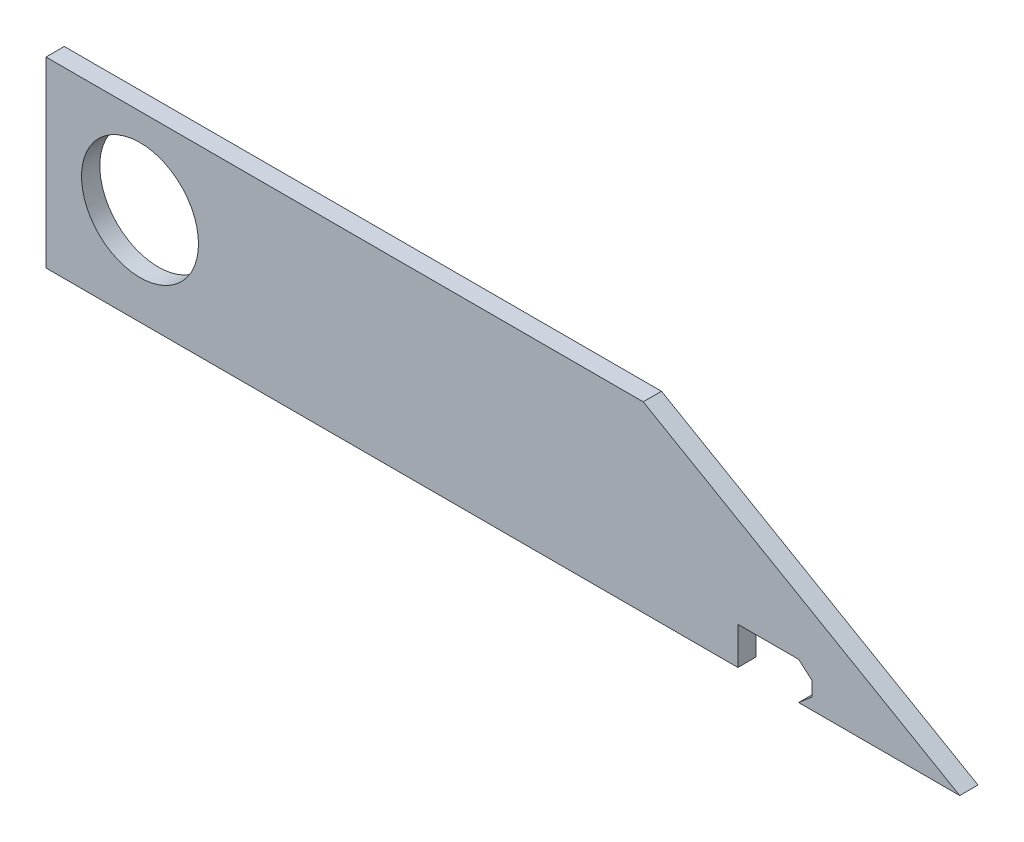
SolidWorks part; units mm, degrees
ref_plane "Front Plane" through (0, 0, 0) normal (0, 0, 1) x (1, 0, 0)
ref_plane "Top Plane" through (0, 0, 0) normal (0, 1, 0) x (1, 0, 0)
ref_plane "Right Plane" through (0, 0, 0) normal (1, 0, 0) x (0, 0, -1)
sketch "Sketch2" plane through (0, 0, 0) normal (0, 0, 1) x (1, 0, 0)
  line L0 (-63.5, 2.4) -> (63.5, 2.4)
  line L1 (63.5, 2.4) -> (19.5059, 27.8)
  line L2 (19.5059, 27.8) -> (-63.5, 27.8)
  line L3 (-63.5, 27.8) -> (-63.5, 2.4)
  dimension "D1" = 25.4
  dimension "D2" = 30
extrude "Boss-Extrude1" add sketch "Sketch2" against normal blind 2.54
sketch "Sketch3" plane through (0, 0, 0) normal (0, 0, 1) x (1, 0, 0)
  circle A0 centre (-50.4348, 15.9061) radius 8.128
extrude "Cut-Extrude1" cut sketch "Sketch3" against normal blind 2.54
sketch "Sketch4" plane through (0, 0, -2.54) normal (0, 0, -1) x (-1, 0, 0)
  line L0 (-41.1054, 7.6) -> (-32.6673, 7.6)
  line L1 (-32.6673, 7.6) -> (-32.6673, 2.4)
  line L2 (63.5, 2.4) -> (-63.5, 2.4) construction
  line L3 (-32.6673, 7.6) -> (-32.6673, 2.4) construction
  line L4 (-32.6673, 2.4) -> (-41.1054, 2.4)
  line L5 (-41.1054, 2.4) -> (-42.9673, 4) construction
  line L6 (-41.1054, 2.4) -> (-42.9673, 4)
  line L7 (-42.9673, 4) -> (-42.9673, 6)
  line L8 (-42.9673, 6) -> (-41.1054, 7.6) construction
  line L9 (-42.9673, 4) -> (-42.9673, 6) construction
  line L10 (-42.9673, 6) -> (-41.1054, 7.6)
extrude "Cut-Extrude2" cut sketch "Sketch4" against normal through all
